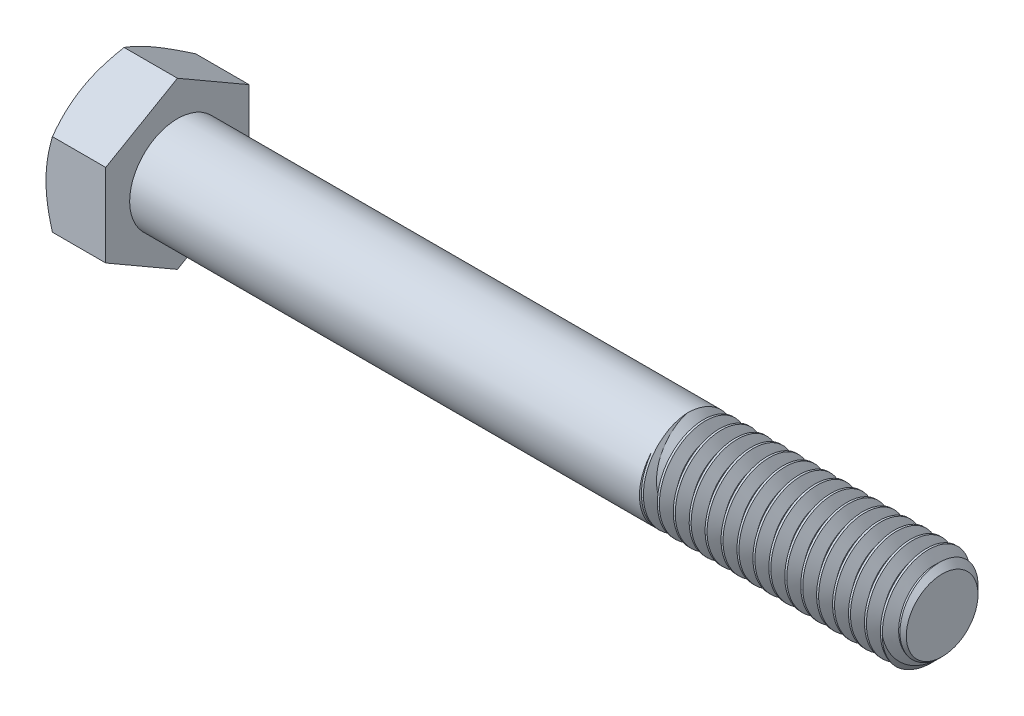
SolidWorks part; units mm, degrees
ref_plane "Front Plane" through (0, 0, 0) normal (0, 0, 1) x (1, 0, 0)
ref_plane "Top Plane" through (0, 0, 0) normal (0, 1, 0) x (1, 0, 0)
ref_plane "Right Plane" through (0, 0, 0) normal (1, 0, 0) x (0, 0, -1)
sketch "Sketch1" plane through (0, 0, 0) normal (0, 0, 1) x (1, 0, 0)
  line L0 (-41.0766, 0) -> (41.0766, 0) construction
  line L1 (41.0766, 4.7625) -> (41.0766, -4.7625) construction
  line L2 (-35.1234, 7.1437) -> (-35.1234, -7.1437) construction
  line L3 (-41.0766, 7.1437) -> (-41.0766, -7.1437) construction
  point P9 (-35.1234, 0)
  point P10 (35.5203, -4.7625)
  dimension "Screw Dia" = 9.525
  dimension "Hex" = 14.2875
  dimension "Head Ht" = 5.9531
  dimension "Screw Lenght" = 76.2
  dimension "D1" = 5.5562
ref_plane "Plane2" through (41.0766, 0, 0) normal (1, 0, 0) x (0, 0, -1)
sketch "Sketch5" plane through (41.0766, 0, 0) normal (1, 0, 0) x (0, 0, -1)
  circle A0 centre (0, 0) radius 4.7625
extrude "Boss-Extrude3" add sketch "Sketch5" against normal up to vertex (76.2 mm away) up to point (-35.1234, 0, 0)
sketch "Sketch9" plane through (41.0766, 0, 0) normal (1, 0, 0) x (0, 0, -1)
  circle A1 centre (0, 0) radius 4.7625
  circle A2 centre (0, 0) radius 4.7625
  dimension "D1" = 0
curve "Helix/Spiral1" pitch 1.5875 height 26.9875 turns 17 parameters "Pitch"=1.5875
chamfer "Chamfer1" distance 1.1906 angle 45 1 edges at (41.0766, 0, -4.7625)
sketch "Sketch10" plane through (0, 0, 0) normal (0, 0, 1) x (1, 0, 0)
  line L0 (41.0766, 4.7625) -> (41.6719, 3.7314)
  line L1 (41.6719, 3.7314) -> (41.8703, 3.7314)
  line L2 (41.8703, 3.7314) -> (42.4656, 4.7625)
  line L3 (41.0766, 4.7625) -> (42.4656, 4.7625)
  line L4 (41.7711, 4.7625) -> (41.7711, 3.7314) construction
  line L5 (41.3742, 4.2469) -> (42.168, 4.2469) construction
  dimension "D1" = 60
  dimension "D2" = 0.1984
  dimension "D3" = 0.7937
sweep "Cut-Sweep1" cut profiles "Sketch10" path "Helix/Spiral1"
sketch "Sketch11" plane through (0, 0, 0) normal (0, 0, 1) x (1, 0, 0)
  line L0 (-35.1234, 4.7625) -> (-35.1234, 0)
  line L1 (-35.1234, 0) -> (20.4391, 0)
  line L3 (20.4391, 0) -> (15.6766, 4.7625)
  line L4 (-35.1234, 4.7625) -> (15.6766, 4.7625)
  dimension "D1" = 45
  dimension "MIn Thread" = 25.4
revolve "Revolve1" add sketch "Sketch11" angle 360 about L1
sketch "Sketch6" plane through (-35.1234, 0, 0) normal (-1, 0, 0) x (0, 0, 1)
  line L0 (0, 7.1437) -> (0, -7.1437) construction
  line L1 (7.1437, 4.1244) -> (0, 8.2489)
  line L2 (0, 8.2489) -> (-7.1437, 4.1244)
  line L3 (-7.1437, 4.1244) -> (-7.1437, -4.1244)
  line L4 (-7.1437, -4.1244) -> (0, -8.2489)
  line L5 (0, -8.2489) -> (7.1437, -4.1244)
  line L6 (7.1437, -4.1244) -> (7.1437, 4.1244)
  circle A0 centre (0, 0) radius 7.1437 construction
extrude "Boss-Extrude4" add sketch "Sketch6" along normal up to vertex (5.9531 mm away) up to point (-41.0766, -7.1437, 0)
sketch "Sketch7" plane through (-41.0766, 0, 0) normal (-1, 0, 0) x (0, 0, 1)
  circle A0 centre (0, 0) radius 7.1437 construction
  circle A1 centre (0, 0) radius 7.1437
sketch "Sketch8" plane through (-41.0766, 0, 0) normal (-1, 0, 0) x (0, 0, 1)
  circle A0 centre (0, 0) radius 7.1437 construction
  circle A1 centre (0, 0) radius 7.1437
extrude "Cut-Extrude3" cut sketch "Sketch8" against normal through all draft 60 flip side to cut
equation "\"D2@Sketch10\" = \"Pitch@Helix/Spiral1\"*.125"
equation "\"D3@Sketch10\" = \"Pitch@Helix/Spiral1\"*.5"
equation "\"D3@Helix/Spiral1\" = \"MIn Thread@Sketch11\"+\"Pitch@Helix/Spiral1\""
equation "\"D1@Chamfer1\" = \"Pitch@Helix/Spiral1\"*.75"
equation "\"D1@Sketch1\" = \"Pitch@Helix/Spiral1\"*3.5"
